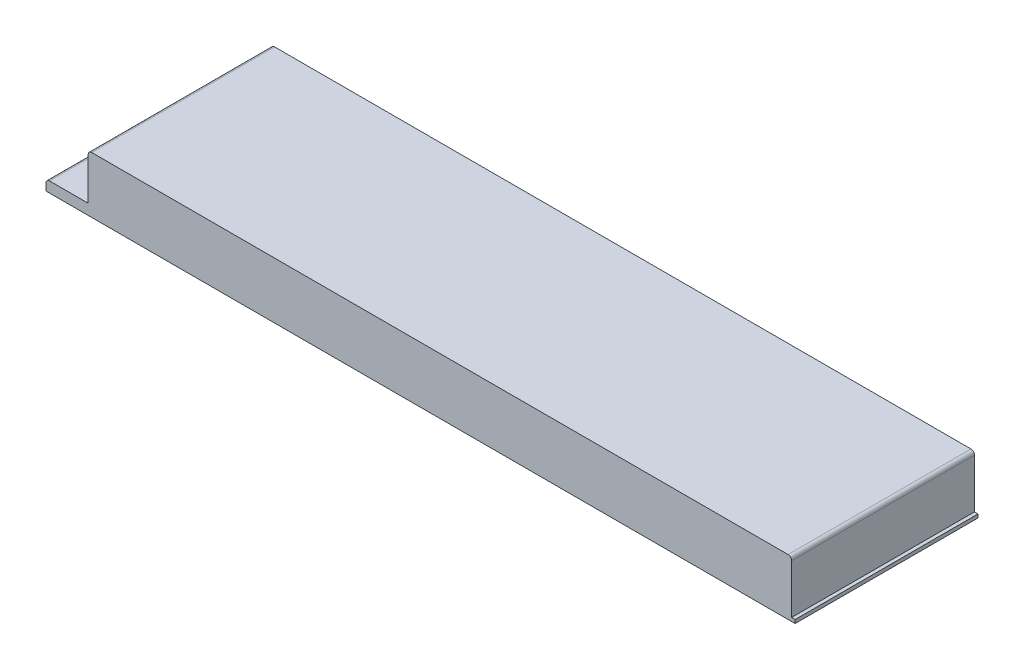
SolidWorks part; units mm, degrees
material "ABS"
ref_plane "Front Plane" through (0, 0, 0) normal (0, 0, 1) x (1, 0, 0)
ref_plane "Top Plane" through (0, 0, 0) normal (0, 1, 0) x (1, 0, 0)
ref_plane "Right Plane" through (0, 0, 0) normal (1, 0, 0) x (0, 0, -1)
sketch "Sketch1" plane through (0, 0, 0) normal (0, 1, 0) x (1, 0, 0)
  line L1 (0, 0) -> (107, 0)
  line L2 (0, 0) -> (0, -26)
  line L3 (0, -26) -> (107, -26)
  line L4 (107, 0) -> (107, -26)
  dimension "D1" = 107
  dimension "D2" = 26
extrude "Boss-Extrude1" add sketch "Sketch1" along normal blind 8 contours L2 L3 L4 L1
sketch "Sketch2" plane through (0, 0, 26) normal (0, 0, 1) x (1, 0, 0)
  line L0 (0, 0) -> (107, 0) construction
  line L1 (107, 8) -> (106, 8)
  line L2 (107, 8) -> (107, 0.5)
  line L3 (107, 0.5) -> (106, 0.5)
  line L4 (106, 8) -> (106, 0.5)
  line L6 (0, 8) -> (6, 8)
  line L7 (0, 8) -> (0, 1.5)
  line L8 (0, 1.5) -> (6, 1.5)
  line L9 (6, 8) -> (6, 1.5)
  dimension "D1" = 1
  dimension "D2" = 0.5
  dimension "D3" = 6
  dimension "D4" = 1.5
extrude "Cut-Extrude1" cut sketch "Sketch2" against normal through all
fillet "Fillet1" radius 0.5 3 edges at (6, 8, 13) (0, 1.5, 13) (106, 8, 13)
sketch "Sketch14" plane through (0, 8, 0) normal (0, 1, 0) x (1, 0, 0)
  line L14 (104.5, -25) -> (104.5, -1)
  line L15 (7.5, -1) -> (7.5, -25)
  line L16 (7.5, -25) -> (104.5, -25)
  line L17 (104.5, -1) -> (7.5, -1)
  line L18 (104.5, -25) -> (104.5, -1)
  line L19 (7.5, -1) -> (7.5, -25)
  line L20 (7.5, -25) -> (104.5, -25)
  line L21 (104.5, -1) -> (7.5, -1)
  dimension "D1" = 1
hole_wizard "CSK for M2 Countersunk Flat Head Screw1" positions "3DSketch1" profile "Sketch16" countersink size "M2" standard "ISO"
sketch3d "3DSketch1"
  point P0 (3, 1.5, 13)
  dimension "D1" = 3
  dimension "D2" = 13
sketch "Sketch16" plane through (3, 1.5, 13) normal (1, 0, 0) x (0, 0, 1)
  line L0 (0, 0) -> (0, 15.721)
  line L1 (0, 15.721) -> (1.2, 15)
  line L2 (1.2, 15) -> (1.2, 1)
  line L3 (1.2, 1) -> (2.2, 0)
  line L5 (2.2, 0) -> (0, 0)
  line L6 (-1.2, 1) -> (-2.2, 0) construction
  line L10 (0, 15.721) -> (-1.2, 15) construction
  line L11 (0, -6.35) -> (0, 107.95) construction
  dimension "Hole Dia." = 2.4
  dimension "Hole Depth" = 15
  dimension "Near C'Sink Dia." = 4.4
  dimension "Near C'Sink Angle" = 90
  dimension "Drill Angle" = 118
extrude "Cut-Extrude7" cut sketch "Sketch14" against normal through all
extrude "Boss-Extrude3" add sketch "Sketch14<3>" against normal blind 1
sketch "Sketch14<3>" plane through (0, 8, 0) normal (0, 1, 0) x (1, 0, 0) same geometry as "Sketch14"
sketch "Sketch18" plane through (0, 0, 0) normal (0, 1, 0) x (1, 0, 0)
  line L1 (7.5, -1) -> (104.5, -1)
  line L2 (7.5, -1) -> (7.5, -25)
  line L3 (7.5, -25) -> (104.5, -25)
  line L4 (104.5, -1) -> (104.5, -25)
extrude "Cut-Extrude8" cut sketch "Sketch18" along normal through all
sketch "Sketch20" plane through (0, 8, 0) normal (0, 1, 0) x (1, 0, 0)
  line L11 (7.5, -1) -> (104.5, -1)
  line L12 (7.5, -1) -> (7.5, -25)
  line L13 (7.5, -25) -> (104.5, -25)
  line L14 (102.5, -23) -> (102.5, -3)
  line L15 (9.5, -23) -> (102.5, -23)
  line L16 (9.5, -3) -> (9.5, -23)
  line L17 (102.5, -3) -> (9.5, -3)
  line L18 (102.5, -23) -> (102.5, -3)
  line L19 (9.5, -23) -> (102.5, -23)
  line L20 (9.5, -3) -> (9.5, -23)
  line L21 (102.5, -3) -> (9.5, -3)
  line L22 (104.5, -1) -> (104.5, -25)
  dimension "D1" = 2
extrude "Boss-Extrude4" add sketch "Sketch20" against normal up to surface (8 mm away) up to face at (56, 0, 13)
extrude "Cut-Extrude9" cut sketch "Sketch20<2>" against normal blind 3
sketch "Sketch20<2>" plane through (0, 8, 0) normal (0, 1, 0) x (1, 0, 0) same geometry as "Sketch20"
sketch "Sketch21" plane through (0, 0, 3) normal (0, 0, 1) x (1, 0, 0)
  line L1 (102.5, 0) -> (50.5, 0)
  line L2 (102.5, 0) -> (102.5, 2)
  line L3 (102.5, 2) -> (50.5, 2)
  line L4 (50.5, 0) -> (50.5, 2)
  dimension "D1" = 52
  dimension "D2" = 2
extrude "Boss-Extrude5" add sketch "Sketch21" along normal blind 5
sketch "Sketch22" plane through (0, 0, 23) normal (0, 0, -1) x (-1, 0, 0)
  line L1 (-102.5, 0) -> (-50.5, 0)
  line L2 (-102.5, 0) -> (-102.5, 2)
  line L3 (-102.5, 2) -> (-50.5, 2)
  line L4 (-50.5, 0) -> (-50.5, 2)
  dimension "D1" = 52
  dimension "D2" = 2
extrude "Boss-Extrude6" add sketch "Sketch22" along normal blind 5
sketch "Sketch23" plane through (0, 0, 26) normal (0, 0, 1) x (1, 0, 0)
  line L1 (107, 0) -> (106.5, 0)
  line L2 (107, 0) -> (107, 16.6122)
  line L3 (107, 16.6122) -> (106.5, 16.6122)
  line L4 (106.5, 0) -> (106.5, 16.6122)
  dimension "D1" = 0.5
extrude "Cut-Extrude10" cut sketch "Sketch23" against normal through all
sketch "Sketch25" plane through (0, 0, 23) normal (0, 0, -1) x (-1, 0, 0)
  line L0 (-9.5, 5) -> (-102.5, 5) construction
  line L1 (-50.5, 0) -> (-48.5, 0)
  line L2 (-50.5, 0) -> (-50.5, 5)
  line L3 (-50.5, 5) -> (-48.5, 5)
  line L4 (-48.5, 0) -> (-48.5, 5)
  dimension "D1" = 2
extrude "Boss-Extrude7" add sketch "Sketch25" along normal up to next
sketch "Sketch26" plane through (50.5, 0, 0) normal (1, 0, 0) x (0, 0, -1)
  line L0 (-8, 2) -> (-3, 2) construction
  line L1 (-18, 0) -> (-8, 0)
  line L2 (-18, 0) -> (-18, 2)
  line L3 (-18, 2) -> (-8, 2)
  line L4 (-8, 0) -> (-8, 2)
extrude "Cut-Extrude11" cut sketch "Sketch26" against normal up to next
sketch "Sketch27" plane through (0, 5, 0) normal (0, 1, 0) x (1, 0, 0)
  line L1 (7.5, -1) -> (104.5, -1)
  line L2 (7.5, -1) -> (7.5, -25)
  line L3 (7.5, -25) -> (104.5, -25)
  line L4 (104.5, -1) -> (104.5, -25)
extrude "Boss-Extrude8" add sketch "Sketch27" along normal up to surface (3 mm away) up to face at (56, 8, 13)
sketch "Sketch29" plane through (48.5, 0, 0) normal (-1, 0, 0) x (0, 0, 1)
  line L0 (3, 0) -> (3, 5) construction
  line L1 (23, 5) -> (3, 5)
  line L2 (23, 5) -> (23, 0)
  line L3 (23, 0) -> (3, 0)
  line L4 (3, 5) -> (3, 0)
extrude "Cut-Extrude12" cut sketch "Sketch29" against normal up to surface (54 mm away) up to face at (102.5, 2.25, 13)
